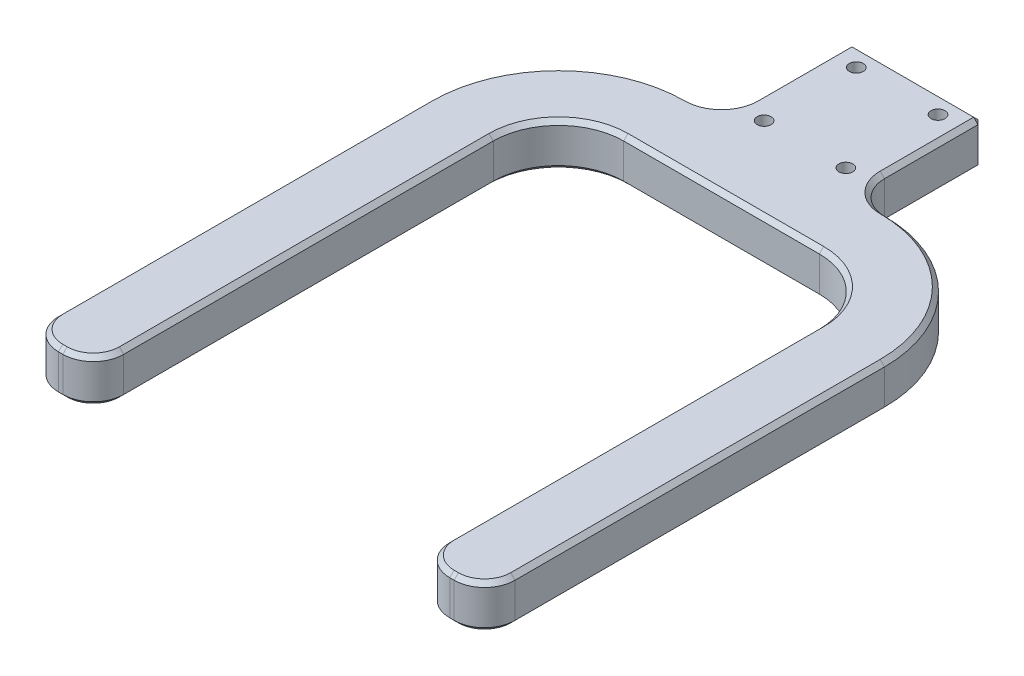
SolidWorks part; units mm, degrees
ref_plane "Front Plane" through (0, 0, 0) normal (0, 0, 1) x (1, 0, 0)
ref_plane "Top Plane" through (0, 0, 0) normal (0, 1, 0) x (1, 0, 0)
ref_plane "Right Plane" through (0, 0, 0) normal (1, 0, 0) x (0, 0, -1)
sketch "Sketch1" plane through (0, 0, 0) normal (0, 1, 0) x (1, 0, 0)
  line L0 (22.5, 57.5) -> (0, 57.5)
  line L1 (0, 57.5) -> (0, 102.5)
  line L2 (37.5, 42.5) -> (37.5, -42.5)
  line L3 (44.5, -49.5) -> (45.5, -49.5)
  line L7 (15, 102.5) -> (0, 102.5)
  line L8 (0, 0) -> (0, 57.5) construction
  line L9 (15, 102.5) -> (15, 72.5)
  line L13 (15, 72.5) -> (22.5, 72.5)
  line L14 (52.5, 42.5) -> (52.5, -42.5)
  arc A0 (37.5, -42.5) -> (44.5, -49.5) centre (44.5, -42.5) ccw
  arc A1 (45.5, -49.5) -> (52.5, -42.5) centre (45.5, -42.5) ccw
  arc A4 (22.5, 57.5) -> (37.5, 42.5) centre (22.5, 42.5) cw
  arc A6 (22.5, 72.5) -> (52.5, 42.5) centre (22.5, 42.5) cw
  circle A7 centre (9.4, 97.9) radius 1.6
  circle A8 centre (9.4, 76.7) radius 1.6
  point P10 (37.5, 0)
  dimension "D7" = 7
  dimension "D8" = 30
  dimension "D9" = 15
  dimension "D10" = 3.2
  dimension "D11" = 18
  dimension "D12" = 3
  dimension "D13" = 4
  dimension "D1" = 15
  dimension "D2" = 15
  dimension "D3" = 30
  dimension "D4" = 30
  dimension "D5" = 75
  dimension "D6" = 107
extrude "Boss-Extrude1" add sketch "Sketch1" along normal blind 10
fillet "Fillet1" radius 7.5 1 edges at (15, 5, -72.5)
chamfer "Chamfer1" distance 1 angle 45 23 edges at (11.25, 0, -57.5) (33.1066, 0, -53.1066) (37.5, 0, 0) (39.5503, 0, 47.4497) (45, 0, 49.5) (50.4497, 0, 47.4497) (52.5, 0, 0) (43.7132, 0, -63.7132) (15, 0, -91.25) (7.5, 0, -102.5) (11.25, 10, -57.5) (33.1066, 10, -53.1066) (37.5, 10, 0) (39.5503, 10, 47.4497) (45, 10, 49.5) (50.4497, 10, 47.4497) (52.5, 10, 0) (43.7132, 10, -63.7132) (15, 10, -91.25) (7.5, 10, -102.5) (17.1967, 0, -74.6967) (17.1967, 10, -74.6967) (15, 5, -102.5)
mirror "Mirror1" about plane through (0, 10, -57.5) normal (1, 0, 0) of bodies 101
